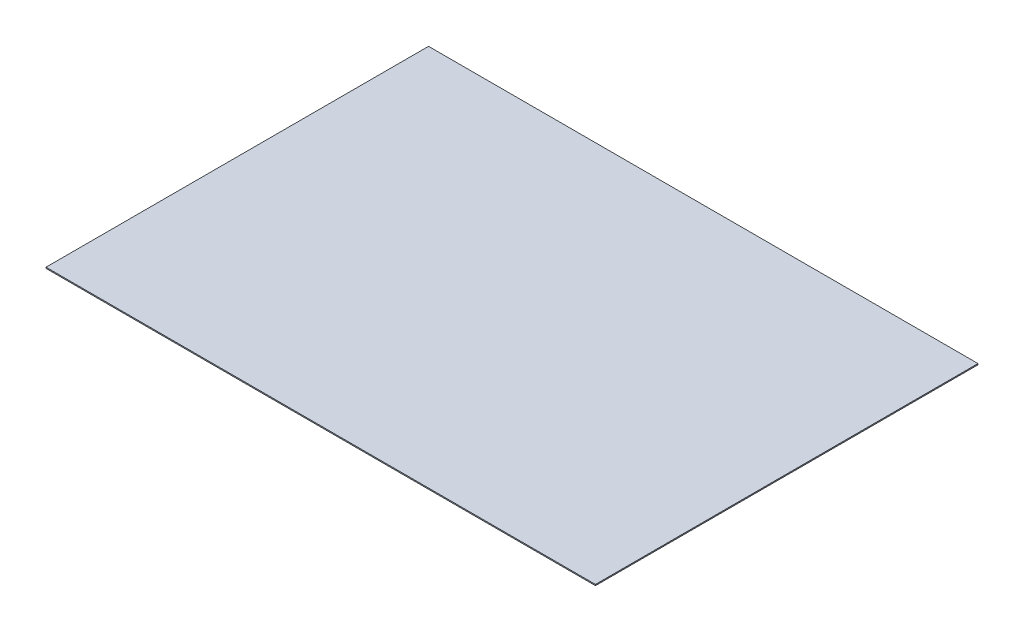
SolidWorks part; units mm, degrees
material "Acrylic (Medium-high impact)"
ref_plane "Front Plane" through (0, 0, 0) normal (0, 0, 1) x (1, 0, 0)
ref_plane "Top Plane" through (0, 0, 0) normal (0, 1, 0) x (1, 0, 0)
ref_plane "Right Plane" through (0, 0, 0) normal (1, 0, 0) x (0, 0, -1)
sketch "Sketch1" plane through (0, 0, 0) normal (0, 1, 0) x (1, 0, 0)
  line L1 (-790, -550) -> (790, -550) construction
  line L2 (-790, -550) -> (-790, 550) construction
  line L3 (-790, 550) -> (790, 550) construction
  line L4 (790, -550) -> (790, 550) construction
  line L5 (-790, -550) -> (790, 550) construction
  line L6 (-790, 550) -> (790, -550) construction
  point P0 (0, 0)
  dimension "Length" = 1580
  dimension "Width" = 1100
sketch "Sketch2" plane through (0, 0, 0) normal (1, 0, 0) x (0, 0, -1)
  line L1 (-550, -1.5875) -> (550, -1.5875) construction
  line L2 (-550, -1.5875) -> (-550, 1.5875) construction
  line L3 (-550, 1.5875) -> (550, 1.5875) construction
  line L4 (550, -1.5875) -> (550, 1.5875) construction
  line L5 (-550, -1.5875) -> (550, 1.5875) construction
  line L6 (-550, 1.5875) -> (550, -1.5875) construction
  dimension "Thickness" = 3.175
sketch "Sketch3" plane through (0, 0, 0) normal (1, 0, 0) x (0, 0, -1)
  line L1 (550, 1.5875) -> (-550, 1.5875)
  line L2 (550, 1.5875) -> (550, -1.5875)
  line L3 (550, -1.5875) -> (-550, -1.5875)
  line L4 (-550, 1.5875) -> (-550, -1.5875)
extrude "Boss-Extrude1" add sketch "Sketch3" against normal up to vertex (790 mm away) and the other way up to vertex (790 mm away) up to point (-790, 0, -550) other way up to point (790, 0, -550)
